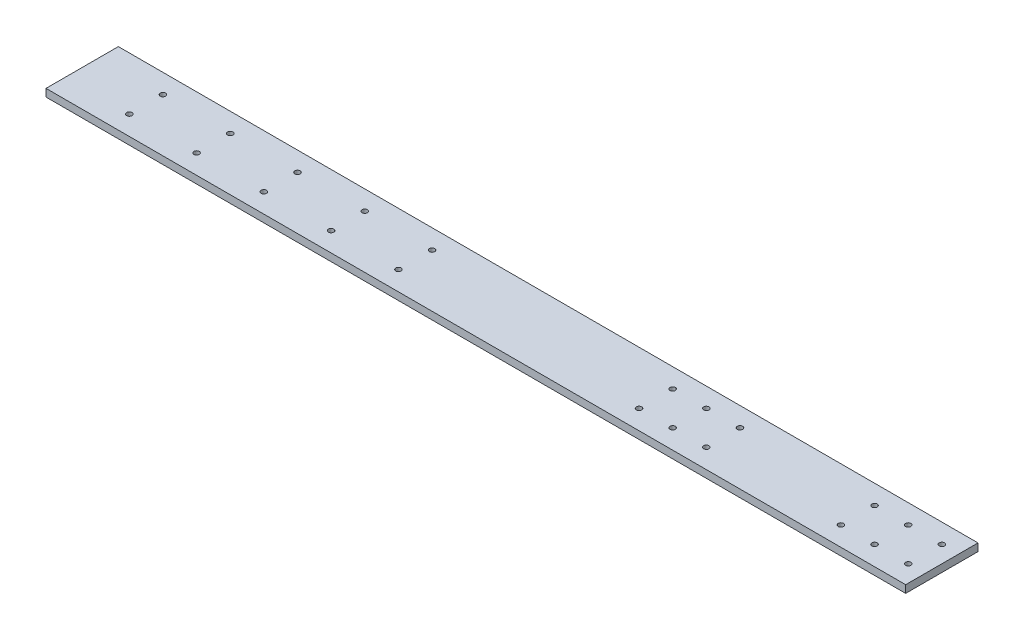
SolidWorks part; units mm, degrees
ref_plane "Front Plane" through (0, 0, 0) normal (0, 0, 1) x (1, 0, 0)
ref_plane "Top Plane" through (0, 0, 0) normal (0, 1, 0) x (1, 0, 0)
ref_plane "Right Plane" through (0, 0, 0) normal (1, 0, 0) x (0, 0, -1)
sketch "Sketch1" plane through (0, 0, 0) normal (0, 1, 0) x (1, 0, 0)
  line L0 (-255.5, 0) -> (-14.5, 0) construction
  line L1 (-255.5, -21.5) -> (255.5, -21.5)
  line L2 (-255.5, -21.5) -> (-255.5, 21.5)
  line L3 (-255.5, 21.5) -> (255.5, 21.5)
  line L4 (255.5, -21.5) -> (255.5, 21.5)
  line L5 (-255.5, -21.5) -> (255.5, 21.5) construction
  line L6 (-255.5, 21.5) -> (255.5, -21.5) construction
  line L7 (-14.5, -35) -> (-14.5, 35) construction
  line L8 (-14.5, 21.5) -> (-14.5, -21.5) construction
  circle A0 centre (-217.5, 10) radius 1.6
  circle A2 centre (-177.5, 10) radius 1.6
  circle A3 centre (-137.5, 10) radius 1.6
  circle A4 centre (-97.5, 10) radius 1.6
  circle A5 centre (-57.5, 10) radius 1.6
  circle A8 centre (-177.5, -10) radius 1.6
  circle A9 centre (-137.5, -10) radius 1.6
  circle A10 centre (-97.5, -10) radius 1.6
  circle A11 centre (-57.5, -10) radius 1.6
  circle A14 centre (-217.5, -10) radius 1.6
  circle A15 centre (225.5, 10) radius 1.6
  circle A16 centre (105.5, 10) radius 1.6
  circle A17 centre (105.5, -10) radius 1.6
  circle A18 centre (225.5, -10) radius 1.6
  circle A19 centre (125.5, -10) radius 1.6
  circle A20 centre (125.5, 10) radius 1.6
  circle A21 centre (245.5, 10) radius 1.6
  circle A22 centre (245.5, -10) radius 1.6
  circle A23 centre (85.5, -10) radius 1.6
  circle A24 centre (85.5, 10) radius 1.6
  circle A25 centre (205.5, 10) radius 1.6
  circle A26 centre (205.5, -10) radius 1.6
  point P0 (0, 0)
  dimension "D4" = 3.2
  dimension "D5" = 5
  dimension "D1" = 511
  dimension "D2" = 43
  dimension "D3" = 10
  dimension "D7" = 38
  dimension "D8" = 30
  dimension "D9" = 240
  dimension "D6" = 2
  dimension "D10" = 2
  dimension "D11" = 2
  dimension "D12" = 2
  dimension "D13" = 2
extrude "Boss-Extrude1" add sketch "Sketch1" along normal blind 4.5
